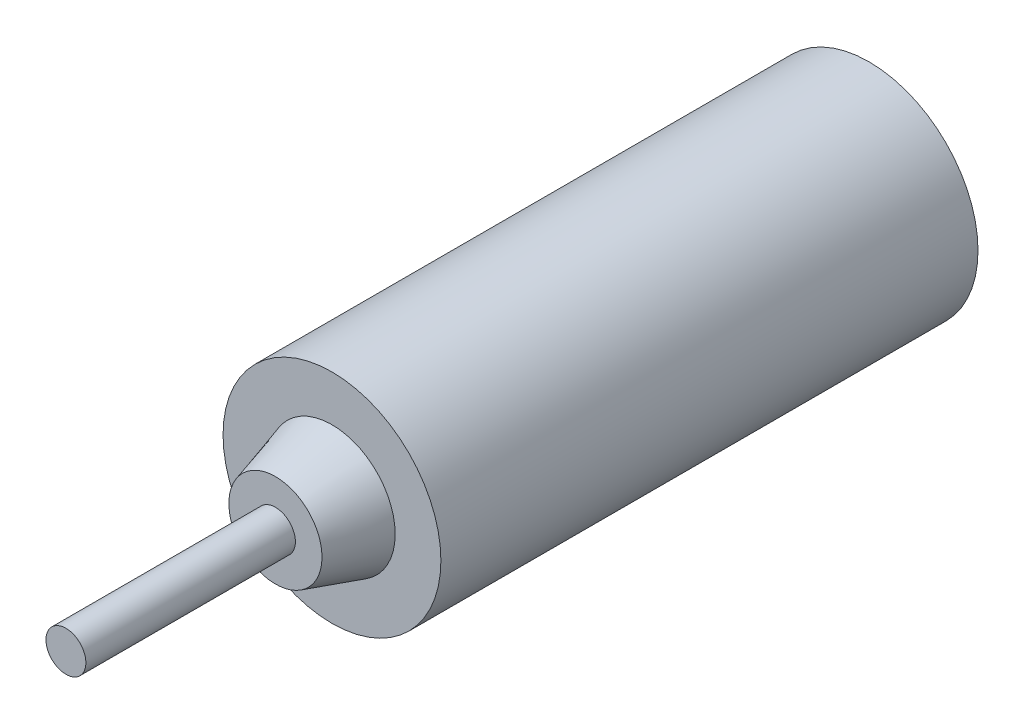
SolidWorks part; units mm, degrees
ref_plane "Front Plane" through (0, 0, 0) normal (0, 0, 1) x (1, 0, 0)
ref_plane "Top Plane" through (0, 0, 0) normal (0, 1, 0) x (1, 0, 0)
ref_plane "Right Plane" through (0, 0, 0) normal (1, 0, 0) x (0, 0, -1)
sketch "Sketch1" plane through (0, 0, 0) normal (0, 0, 1) x (1, 0, 0)
  circle A0 centre (0, 0) radius 32.75
  dimension "D1" = 65.5
extrude "Boss-Extrude1" add sketch "Sketch1" against normal mid plane 161.5
sketch "Sketch10" plane through (0, 0, 0) normal (1, 0, 0) x (0, 0, -1)
  line L0 (-97.75, 0) -> (-97.75, 14)
  line L1 (-80.75, 19) -> (-97.75, 14)
  line L2 (-1000, 0) -> (49000, 0) construction
  line L3 (-97.75, 0) -> (-80.75, 0)
  line L4 (-80.75, 0) -> (-80.75, 19)
  line L6 (-80.75, 32.75) -> (-80.75, -32.75) construction
  point P3 (-97.75, 0)
  dimension "D1" = 14
  dimension "D2" = 17
  dimension "D3" = 19
revolve "Revolve1" add sketch "Sketch10" angle 360 about L2
sketch "Sketch12" plane through (0, 0, 97.75) normal (0, 0, 1) x (1, 0, 0)
  circle A0 centre (0, 0) radius 6
  dimension "D1" = 12
extrude "Boss-Extrude5" add sketch "Sketch12" along normal blind 63
